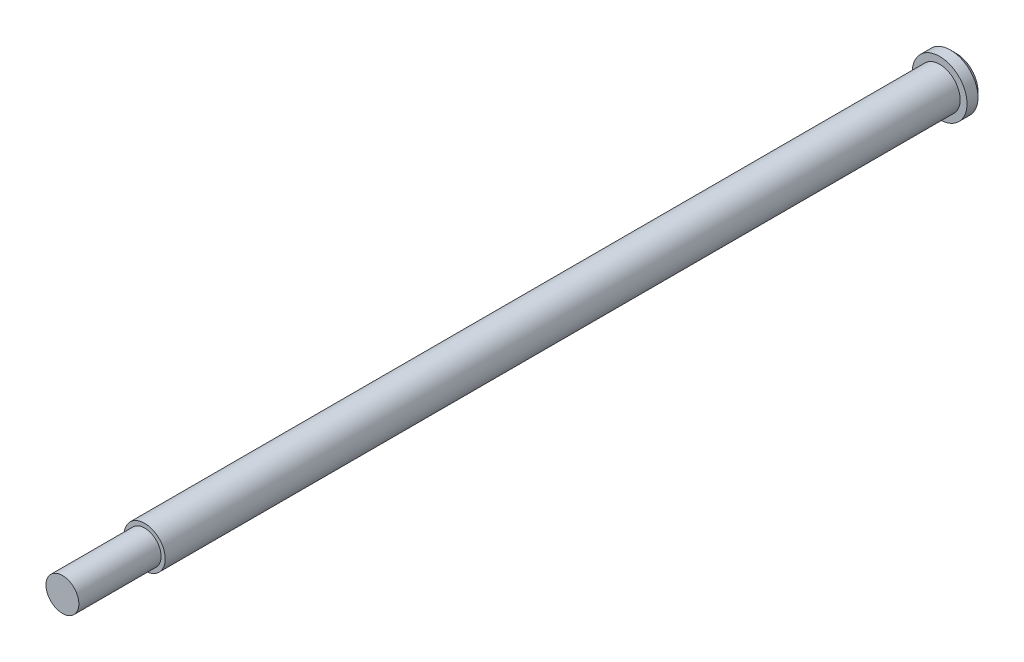
SolidWorks part; units mm, degrees
material "镀铬不锈钢"
ref_plane "前视基准面" through (0, 0, 0) normal (0, 0, 1) x (1, 0, 0)
ref_plane "上视基准面" through (0, 0, 0) normal (0, 1, 0) x (1, 0, 0)
ref_plane "右视基准面" through (0, 0, 0) normal (1, 0, 0) x (0, 0, -1)
sketch "草图1" plane through (0, 0, 0) normal (0, 0, 1) x (1, 0, 0)
  circle A0 centre (0, 0) radius 3
  dimension "D1" = 6
extrude "凸台-拉伸1" add sketch "草图1" along normal blind 160
sketch "草图2" plane through (0, 0, 0) normal (0, 1, 0) x (1, 0, 0)
  line L0 (0, 0) -> (5, 0)
  line L1 (0, 0) -> (0, 3)
  line L2 (5, 0) -> (5, 3)
  line L3 (5, 3) -> (0, 3)
  dimension "D1" = 5
  dimension "D2" = 3
revolve "旋转1" add sketch "草图2" angle 360 about L1
sketch "草图3" plane through (0, 0, 0) normal (0, 0, 1) x (1, 0, 0)
  circle A0 centre (0, 0) radius 3.75
  dimension "D1" = 7.5
extrude "凸台-拉伸2" add sketch "草图3" along normal offset from surface (145 mm away) 15 up to face at (3, 0, 160)
chamfer "倒角1" distance 1 angle 45 1 edges at (5, 0, -3)
sketch "草图4" plane through (0, 0, 160) normal (0, 0, 1) x (1, 0, 0)
  circle A0 centre (0, 0) radius 3
